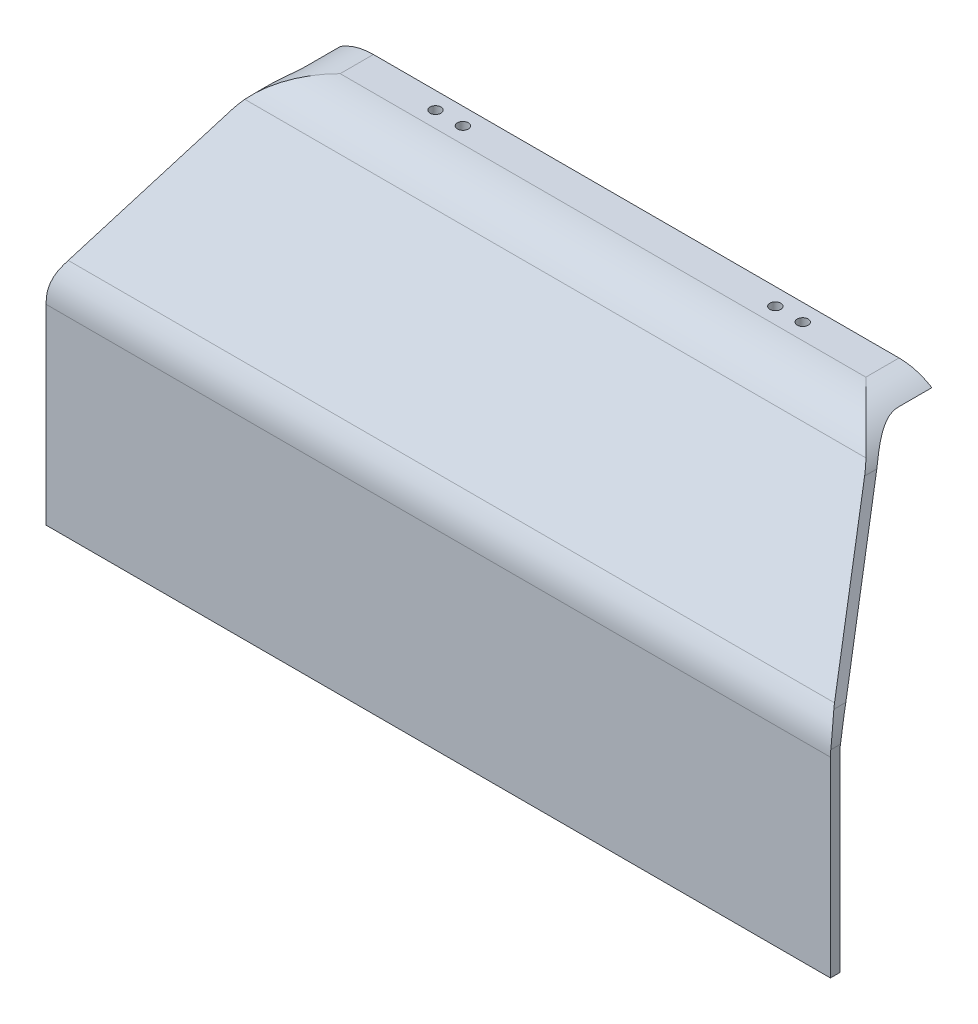
SolidWorks part; units mm, degrees
ref_plane "Alzado" through (0, 0, 0) normal (0, 0, 1) x (1, 0, 0)
ref_plane "Planta" through (0, 0, 0) normal (0, 1, 0) x (1, 0, 0)
ref_plane "Vista lateral" through (0, 0, 0) normal (1, 0, 0) x (0, 0, -1)
sketch "Croquis1" plane through (0, 0, 0) normal (1, 0, 0) x (0, 0, -1)
  line L0 (0, 0) -> (0, 66.9081)
  line L1 (0, 66.9081) -> (41.9998, 116.9615)
  line L2 (41.9998, 116.9615) -> (60.6009, 116.9615)
  line L3 (60.6009, 116.9615) -> (60.6009, 119.9615)
  line L4 (60.6009, 119.9615) -> (40.6009, 119.9615)
  line L5 (40.6009, 119.9615) -> (-3, 68)
  line L6 (-3, 68) -> (-3, 0)
  line L7 (-3, 0) -> (0, 0)
  line L8 (0, 66.9081) -> (29.2398, 66.9081) construction
  dimension "D1" = 3
  dimension "D2" = 3
  dimension "D3" = 3
  dimension "D4" = 68
  dimension "D5" = 119.9615
  dimension "D6" = 20
  dimension "D7" = 50
extrude "Saliente-Extruir1" add sketch "Croquis1" along normal mid plane 252
fillet "Redondeo1" radius 18 1 edges at (0, 68, 3)
fillet "Redondeo2" radius 20 1 edges at (0, 119.9615, -40.6009)
fillet "Redondeo3" radius 17 1 edges at (0, 116.9615, -41.9998)
fillet "Redondeo4" radius 17 1 edges at (0, 66.9081, 0)
sketch "Croquis2" plane through (0, 0, 3) normal (0, 0, 1) x (1, 0, 0)
  line L29 (-96, 119.9615) -> (-126, 68)
  line L35 (-96, 119.9615) -> (-126, 119.9615)
  line L36 (-126, 119.9615) -> (-126, 68)
  dimension "D5" = 60
extrude "Cortar-Extruir1" cut sketch "Croquis2" against normal through all
mirror "Simetría1" about plane through (0, 0, 0) normal (1, 0, 0) of "Cortar-Extruir1"
fillet "Redondeo5" radius 17 2 edges at (-126, 68, 0.064) (126, 68, 0.064)
sketch "Croquis5" plane through (0, 0, -60.6009) normal (0, 0, -1) x (-1, 0, 0)
  line L0 (84.453, 119.9615) -> (96, 119.9615)
  line L1 (96, 119.9615) -> (101.7735, 109.9615)
  arc A0 (101.7735, 109.9615) -> (84.453, 119.9615) centre (84.453, 99.9615) ccw
extrude "Cortar-Extruir2" cut sketch "Croquis5" against normal through all
mirror "Simetría2" about plane through (0, 0, 0) normal (1, 0, 0) of "Cortar-Extruir2"
sketch "Croquis6" plane through (0, 119.9615, 0) normal (0, 1, 0) x (1, 0, 0)
  circle A0 centre (-59, 55.1009) radius 1.75
  circle A1 centre (-50.2, 55.1009) radius 1.75
extrude "Cortar-Extruir3" cut sketch "Croquis6" against normal blind 20
mirror "Simetría3" about plane through (0, 0, 0) normal (1, 0, 0) of "Cortar-Extruir3"
